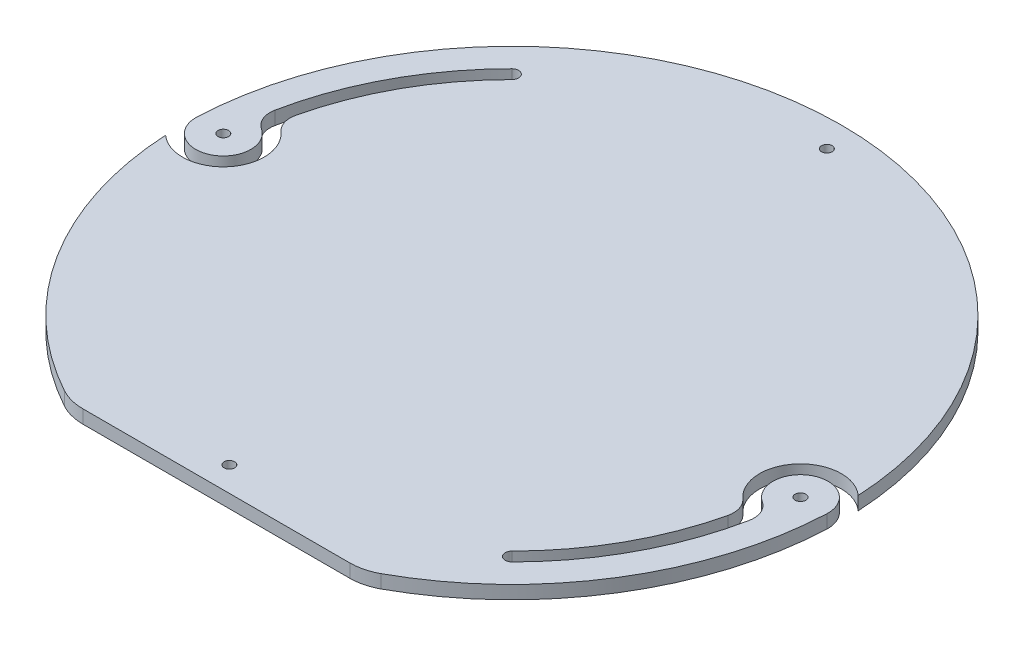
SolidWorks part; units mm, degrees
material "ABS"
ref_plane "Front Plane" through (0, 0, 0) normal (0, 0, 1) x (1, 0, 0)
ref_plane "Top Plane" through (0, 0, 0) normal (0, 1, 0) x (1, 0, 0)
ref_plane "Right Plane" through (0, 0, 0) normal (1, 0, 0) x (0, 0, -1)
sketch "Sketch1" plane through (0, 0, 0) normal (0, 1, 0) x (1, 0, 0)
  line L0 (-30.03, -64.8129) -> (30.03, -64.8129) construction
  line L1 (0, -85) -> (0, 0) construction
  line L2 (0, -85) -> (32.4891, -64.8129) construction
  line L3 (-30.03, -66.5129) -> (30.03, -66.5129)
  arc A0 (34.8348, -63.5829) -> (-34.8348, -63.5829) centre (0, 0) ccw construction
  circle A1 centre (0, -85) radius 38.25 construction
  arc A2 (30.03, -64.8129) -> (34.8348, -63.5829) centre (30.03, -54.8129) ccw construction
  arc A3 (-30.03, -64.8129) -> (-34.8348, -63.5829) centre (-30.03, -54.8129) cw construction
  arc A4 (35.6516, -65.0738) -> (-35.6516, -65.0738) centre (0, 0) ccw
  arc A5 (-30.03, -66.5129) -> (-35.6516, -65.0738) centre (-30.03, -54.8129) cw
  arc A6 (30.03, -66.5129) -> (35.6516, -65.0738) centre (30.03, -54.8129) ccw
  dimension "D1" = 145
  dimension "D2" = 76.5
  dimension "D4" = 10
  dimension "D3" = 85
  dimension "D5" = 1.7
extrude "Boss-Extrude1" add sketch "Sketch1" along normal blind 3
sketch "Sketch2" plane through (0, 3, 0) normal (0, 1, 0) x (1, 0, 0)
  line L0 (0, 0) -> (2.9661, 67.9353) construction
  line L1 (0, 0) -> (-2.6608, -60.9419) construction
  line L2 (0, 0) -> (-67.9353, 2.9661) construction
  line L3 (0, 0) -> (67.9353, -2.9661) construction
  line L4 (0, 0) -> (0, -66.5129) construction
  line L5 (-30.03, -66.5129) -> (30.03, -66.5129) construction
  circle A0 centre (-2.6608, -60.9419) radius 1.2
  circle A1 centre (-67.9353, 2.9661) radius 1.2
  circle A2 centre (2.9661, 67.9353) radius 1.2
  circle A3 centre (67.9353, -2.9661) radius 1.2
  dimension "D4" = 2.4
  dimension "D1" = 68
  dimension "D2" = 61
  dimension "D3" = 2.5
extrude "Cut-Extrude1" cut sketch "Sketch2" against normal through all
sketch "Sketch3" plane through (0, 3, 0) normal (0, 1, 0) x (1, 0, 0)
  line L0 (-48.0833, 48.0833) -> (-45.9619, 45.9619) construction
  line L1 (0, 0) -> (-74.2, 0) construction
  line L2 (-61.7353, 2.9661) -> (-58.7353, 2.9661) construction
  line L3 (48.0833, -48.0833) -> (45.9619, -45.9619) construction
  line L4 (0, 0) -> (74.2, 0) construction
  line L5 (61.7353, -2.9661) -> (58.7353, -2.9661) construction
  arc A0 (-74.1294, 3.2366) -> (-64.5294, 8.1468) centre (-67.9353, 2.9661) ccw
  arc A1 (35.6516, -65.0738) -> (-35.6516, -65.0738) centre (0, 0) ccw construction
  arc A2 (-66.6861, 13.303) -> (-48.0833, 48.0833) centre (0, 0) cw
  arc A3 (-45.9619, 45.9619) -> (-63.3242, 14.6643) centre (0, 0) ccw
  arc A4 (-61.7919, 9.8144) -> (-74.0993, -3.8635) centre (-67.9353, 2.9661) cw
  arc A5 (-74.0993, -3.8635) -> (-74.1294, 3.2366) centre (0, 0) cw
  arc A6 (-45.9619, 45.9619) -> (-48.0833, 48.0833) centre (-47.0226, 47.0226) ccw
  arc A7 (-63.3242, 14.6643) -> (-61.7919, 9.8144) centre (-58.4531, 13.5363) ccw
  arc A8 (-64.5294, 8.1468) -> (-66.6861, 13.303) centre (-61.7827, 12.3248) cw
  arc A9 (74.1294, -3.2366) -> (64.5294, -8.1468) centre (67.9353, -2.9661) ccw
  arc A10 (66.6861, -13.303) -> (48.0833, -48.0833) centre (0, 0) cw
  arc A11 (45.9619, -45.9619) -> (63.3242, -14.6643) centre (0, 0) ccw
  arc A12 (61.7919, -9.8144) -> (74.0993, 3.8635) centre (67.9353, -2.9661) cw
  arc A13 (74.0993, 3.8635) -> (74.1294, -3.2366) centre (0, 0) cw
  arc A14 (45.9619, -45.9619) -> (48.0833, -48.0833) centre (47.0226, -47.0226) ccw
  arc A15 (63.3242, -14.6643) -> (61.7919, -9.8144) centre (58.4531, -13.5363) ccw
  arc A16 (64.5294, -8.1468) -> (66.6861, -13.303) centre (61.7827, -12.3248) cw
  point P22 (67.9353, -2.9661)
  point P39 (0, 0)
  dimension "D3" = 5
  dimension "D1" = 3
  dimension "D2" = 45
  dimension "D4" = 2
extrude "Cut-Extrude2" cut sketch "Sketch3" against normal through all
equation "\"smallPulleyTeeth\"= 30"
equation "\"largePulleyTeeth\"= 30"
equation "\"eighthThick\"= 3.0mm"
equation "\"sixteenthThick\" = 1.7mm"
equation "\"quarterThick\"=6.0mm"
equation "\"OD\" = 145mm"
equation "\"puckAngle\" = 60.5deg"
equation "\"puckDiam\" = 76.5mm"
equation "\"axlePress\" = 5.9mm"
equation "\"press\" = 0.2mm"
equation "\"wheelClear\" = 0.3mm"
equation "\"10-32clear\" = 4.8mm"
equation "\"6-32clear\" = 3.3mm"
equation "\"8-32clear\" = 4.0mm"
equation "\"4-40clear\" = 3.0mm"
equation "\"wheelHeight\" = 22mm"
equation "\"wheelWell\" = 65mm"
equation "\"D1@Sketch1\"=\"OD\""
equation "\"D1@Boss-Extrude1\"=\"eighthThick\""
equation "\"D2@Sketch1\"=\"puckDiam\""
equation "\"puckDist\" = 85mm"
equation "\"scoopFillet\" = 5mm"
equation "\"10-32tap\" = 4.45mm"
equation "\"ledSmall\" = 3.1mm"
equation "\"ledLarge\" = 4.2mm"
equation "\"ledLength\" = 4.2mm"
equation "\"D3@Sketch1\"=\"puckDist\""
equation "\"D5@Sketch1\"=\"sixteenthThick\""
